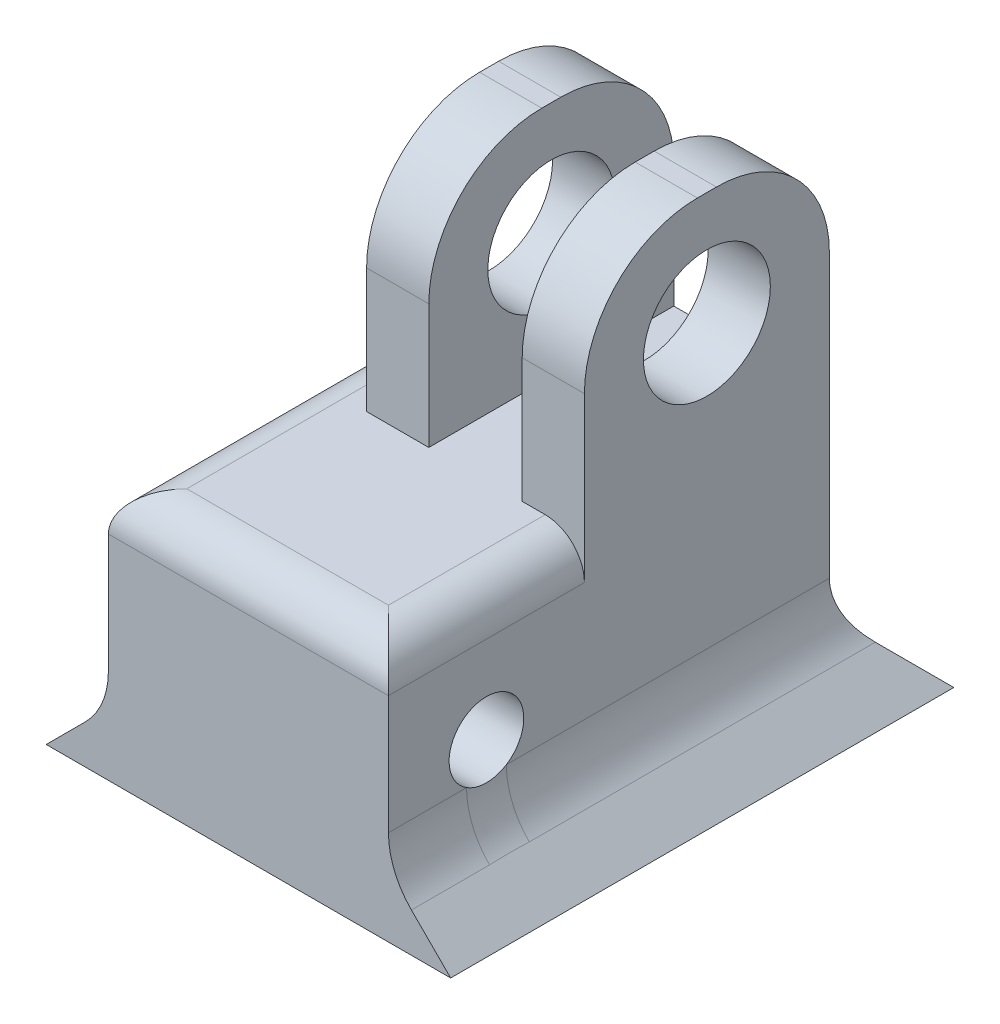
SolidWorks part; units mm, degrees
ref_plane "Front Plane" through (0, 0, 0) normal (0, 0, 1) x (1, 0, 0)
ref_plane "Top Plane" through (0, 0, 0) normal (0, 1, 0) x (1, 0, 0)
ref_plane "Right Plane" through (0, 0, 0) normal (1, 0, 0) x (0, 0, -1)
sketch "Sketch1" plane through (0, 0, 0) normal (0, 0, 1) x (1, 0, 0)
  line L1 (-14.29, -25) -> (14.29, -25)
  line L2 (-14.29, -25) -> (-14.29, 25)
  line L3 (-14.29, 25) -> (14.29, 25)
  line L4 (14.29, -25) -> (14.29, 25)
  line L5 (-14.29, -25) -> (14.29, 25) construction
  line L6 (-14.29, 25) -> (14.29, -25) construction
  point P0 (0, 0)
  dimension "D1" = 50
  dimension "D2" = 28.58
extrude "Boss-Extrude1" add sketch "Sketch1" along normal mid plane 25
sketch "Sketch2" plane through (0, 0, 12.5) normal (0, 0, 1) x (-1, 0, 0)
  line L1 (-7.94, -0.775) -> (1.59, -0.775)
  line L2 (-7.94, -0.775) -> (-7.94, -25)
  line L3 (-7.94, -25) -> (1.59, -25)
  line L4 (1.59, -0.775) -> (1.59, -25)
  line L5 (7.94, -0.775) -> (14.29, -0.775)
  line L6 (7.94, -0.775) -> (7.94, -25)
  line L7 (7.94, -25) -> (14.29, -25)
  line L8 (14.29, -0.775) -> (14.29, -25)
  line L10 (-14.29, -25) -> (14.29, -25) construction
  line L11 (14.29, -25) -> (14.29, 25) construction
  line L12 (-14.29, 25) -> (-14.29, -25) construction
  dimension "D1" = 6.35
  dimension "D2" = 6.35
  dimension "D3" = 24.225
  dimension "D4" = 6.35
extrude "Cut-Extrude1" cut sketch "Sketch2" against normal through all
fillet "Fillet1" radius 11.53 4 edges at (-4.765, 25, -12.5) (-4.765, 25, 12.5) (11.115, 25, 12.5) (11.115, 25, -12.5)
sketch "Sketch3" plane through (14.29, 0, 0) normal (1, 0, 0) x (0, 0, -1)
  line L0 (-11.4063, 13.47) -> (20.1617, 13.47) construction
  line L1 (0, 37.5) -> (0, -49962.5) construction
  line L2 (-0.97, 25) -> (0.97, 25) construction
  circle A0 centre (0, 13.47) radius 6.477
  point P9 (0, 25)
  dimension "D1" = 12.954
extrude "Cut-Extrude2" cut sketch "Sketch3" against normal through all
sketch "Sketch4" plane through (14.29, 0, 0) normal (1, 0, 0) x (0, 0, -1)
  line L0 (-15.659, -25) -> (49984.341, -25) construction
  line L2 (-12.5, -25) -> (12.5, -25) construction
  line L3 (18.85, -25) -> (12.5, -18.65)
  line L4 (12.5, -25) -> (12.5, 13.47) construction
  line L5 (12.5, -18.65) -> (12.5, -25)
  line L6 (12.5, -25) -> (18.85, -25)
  dimension "D1" = 6.35
  dimension "D2" = 45
extrude "Boss-Extrude2" add sketch "Sketch4" against normal up to surface (28.58 mm away) up to face at (-14.29, -12.1125, 0)
sketch "Sketch5" plane through (0, 0, 12.5) normal (0, 0, 1) x (1, 0, 0)
  line L0 (-1.59, 0.775) -> (7.94, 0.775) construction
  line L1 (-14.29, -25) -> (14.29, -25)
  line L2 (-14.29, -25) -> (-14.29, 0.775)
  line L3 (-14.29, 0.775) -> (14.29, 0.775)
  line L4 (14.29, -25) -> (14.29, 0.775)
  line L5 (14.29, -25) -> (14.29, 13.47) construction
extrude "Boss-Extrude3" add sketch "Sketch5" along normal blind 20
sketch "Sketch6" plane through (14.29, 0, 0) normal (1, 0, 0) x (0, 0, -1)
  line L0 (-22.5, 0.775) -> (-22.5, -27.4392) construction
  line L2 (-29.7474, -12.1125) -> (-35.2025, -12.1125) construction
  line L4 (-32.5, 0.775) -> (-12.5, 0.775) construction
  circle A0 centre (-22.5, -12.1125) radius 3.81
  point P10 (-22.5, 0.775)
  dimension "D1" = 7.62
extrude "Cut-Extrude3" cut sketch "Sketch6" against normal through all both and the other way through all
sketch "Sketch7" plane through (0, 0, -12.5) normal (0, 0, -1) x (-1, 0, 0)
  line L0 (-14.29, -25) -> (-20.64, -25)
  line L1 (-20.64, -25) -> (-14.29, -18.65)
  line L2 (-14.29, -18.65) -> (-14.29, 13.47) construction
  line L3 (14.29, -25) -> (-14.29, -25) construction
  line L4 (-14.29, -25) -> (-14.29, -18.65) construction
  line L5 (-14.29, -18.65) -> (-14.29, -25)
  dimension "D1" = 45
  dimension "D2" = 6.35
extrude "Boss-Extrude4" add sketch "Sketch7" against normal up to surface and the other way up to surface up to face at (0, -12.1125, 32.5) other way up to face at (0, -21.825, -15.675)
mirror "Mirror2" about plane through (0, 0, 0) normal (1, 0, 0) of "Boss-Extrude4"
hole_wizard "Ø5.0mm Dowel Hole1" positions "Sketch9" profile "Sketch11" hole size "Ø5.0" standard "ANSI Metric"
sketch "Sketch9" plane through (0, -25, 0) normal (0, -1, 0) x (-1, 0, 0)
  line L0 (-7.5, -14.325) -> (7.5, 0.675) construction
  line L2 (-7.5, 0.675) -> (7.5, -14.325) construction
  line L5 (0, -32.5) -> (0, 18.85) construction
  line L6 (20.64, -32.5) -> (-20.64, -32.5) construction
  line L7 (20.64, 18.85) -> (-20.64, 18.85) construction
  line L9 (-20.64, -6.825) -> (20.64, -6.825) construction
  line L10 (-20.64, -32.5) -> (-20.64, 18.85) construction
  line L11 (20.64, -32.5) -> (20.64, 18.85) construction
  point P0 (-7.5, 0.675)
  point P3 (7.5, 0.675)
  point P6 (7.5, -14.325)
  point P9 (-7.5, -14.325)
  point P48 (0, -6.825)
  point P49 (12.2837, -14.325)
  dimension "D1" = 15
  dimension "D2" = 15
sketch "Sketch11" plane through (7.5, -25, -0.675) normal (1, 0, 0) x (0, 0, -1)
  line L0 (0, 0) -> (0, 11.5022)
  line L1 (0, 11.5022) -> (2.5, 10)
  line L2 (2.5, 10) -> (2.5, 0)
  line L5 (2.5, 0) -> (0, 0)
  line L10 (0, 11.5022) -> (-2.5, 10) construction
  line L11 (0, -6.35) -> (0, 107.95) construction
  dimension "Hole Dia." = 5
  dimension "Hole Depth" = 10
  dimension "Drill Angle" = 118
fillet "Fillet2" radius 8 3 edges at (-14.29, -18.65, 10) (14.29, -18.65, 10) (0, -18.65, -12.5)
fillet "Fillet4" radius 4 3 edges at (14.29, 0.775, 22.5) (0, 0.775, 32.5) (-14.29, 0.775, 10)
